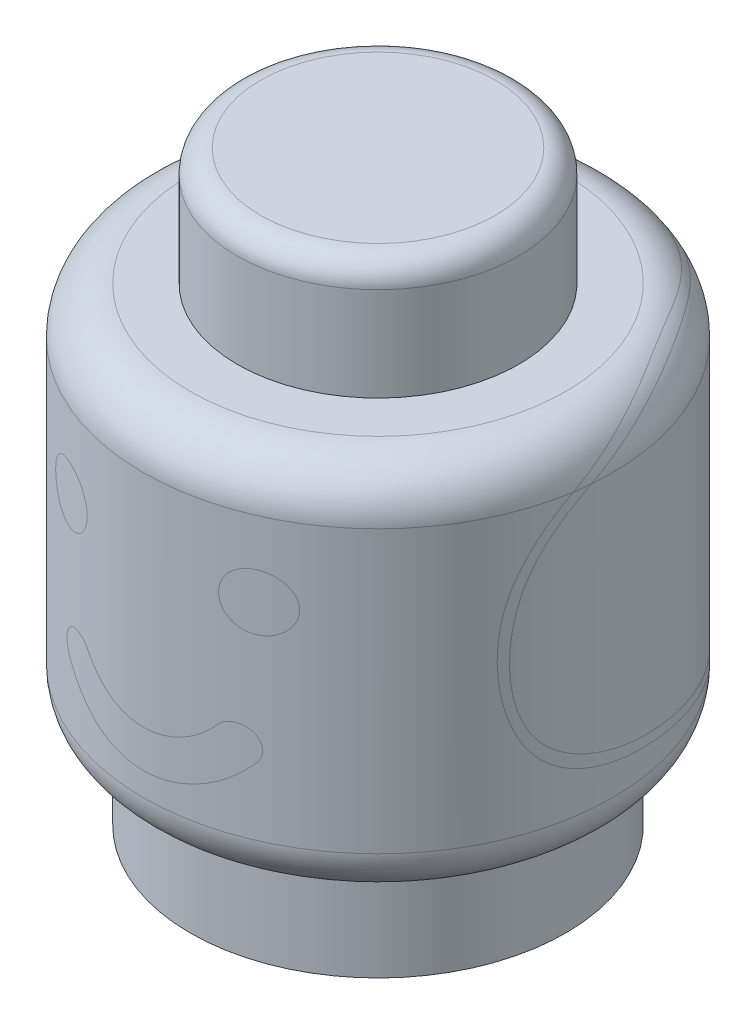
SolidWorks part; units mm, degrees
material "ABS"
ref_plane "Front" through (0, 0, 0) normal (0, 0, 1) x (1, 0, 0)
ref_plane "Top" through (0, 0, 0) normal (0, 1, 0) x (1, 0, 0)
ref_plane "Right" through (0, 0, 0) normal (1, 0, 0) x (0, 0, -1)
sketch "Sketch1" plane through (0, 0, 0) normal (0, 1, 0) x (1, 0, 0)
  circle A0 centre (0, 0) radius 5
  dimension "D1" = 10
sketch "Sketch3" plane through (0, 0, 0) normal (0, 1, 0) x (1, 0, 0)
  circle A0 centre (0, 0) radius 4
  dimension "D1" = 8
extrude "Head" add sketch "Sketch1" along normal blind 8
extrude "Neck" add sketch "Sketch3" against normal blind 2 contours A0
sketch "Sketch6" plane through (0, 8, 0) normal (0, 1, 0) x (1, 0, 0)
  circle A0 centre (0, 0) radius 3
  dimension "D1" = 6
extrude "Head knob" add sketch "Sketch6" along normal blind 2.5
hole_wizard "Head hole" positions "Sketch8" profile "Sketch7" hole size "Ø6.0" standard "ANSI Metric"
sketch "Sketch8" plane through (0, -2, 0) normal (0, -1, 0) x (-1, 0, 0)
  point P0 (0, 0)
sketch "Sketch7" plane through (0, -2, 0) normal (1, 0, 0) x (0, 0, -1)
  line L0 (0, 0) -> (0, 6.8026)
  line L1 (0, 6.8026) -> (3, 5)
  line L2 (3, 5) -> (3, 0)
  line L5 (3, 0) -> (0, 0)
  line L10 (0, 6.8026) -> (-3, 5) construction
  line L11 (0, -6.35) -> (0, 107.95) construction
  dimension "Hole Dia." = 6
  dimension "Hole Depth" = 5
  dimension "Drill Angle" = 118
fillet "Head roundness" radius 1 2 edges at (0, 0, 5) (0, 8, 5)
fillet "Smoothing edges" [suppressed] radius 0.1
fillet "Eady insert" radius 0.5 1 edges at (0, 10.5, 3)
sketch "Sketch9" plane through (0, 0, 0) normal (1, 0, 0) x (0, 0, -1)
  line L2 (-5, 7) -> (5, 7) construction
  line L3 (-0.4285, 7) -> (-0.5368, 7.1682) construction
  line L4 (-1.7145, 5.2338) -> (-1.9078, 5.2848) construction
  line L5 (-1.4811, 2.7691) -> (-1.6394, 2.6642) construction
  line L6 (4.9547, 7.2975) -> (5.0299, 7.4828) construction
  line L7 (8.9952, 4.1399) -> (9.1952, 4.1399) construction
  line L8 (4.9368, 0.6502) -> (4.8494, 0.416) construction
  arc A1 (4, 0) -> (5, 1) centre (4, 1) ccw construction
  arc A2 (5, 7) -> (4, 8) centre (4, 7) ccw construction
  spline S0 degree 3 poles (-0.3026, 7.6263) (-1.9595, 5.4032) (-1.8267, 1.2263) (2.4733, 2.0171) (6.7864, -0.4197) (10.8087, 5.0886) (6.7128, 6.5274) (3.1598, 8.0929) (-0.3026, 7.6263) (-1.9595, 5.4032) (-1.8267, 1.2263) knots -0.30846 -0.270009 -0.095471 0 0.100272 0.311612 0.353587 0.520022 0.69154 0.729991 0.904529 1 1.100272 1.311612 1.353587 only from (-1.7145, 5.2338) to (-1.7145, 5.2338)
  spline S1 degree 3 poles (-1.1206, 6.855) (-2.2574, 5.2283) (-1.6994, 0.8168) (1.903, 2.0367) (7.2209, -0.9272) (10.8858, 4.8178) (7.019, 6.935) (3.1436, 8.0116) (0.9956, 8.0417) (-1.1206, 6.855) (-2.2574, 5.2283) (-1.6994, 0.8168) knots -0.258073 -0.101406 -0.07364 0 0.09253 0.309613 0.353835 0.53475 0.703584 0.741927 0.898594 0.92636 1 1.09253 1.309613 1.353835 only from (-1.9078, 5.2848) to (-1.9078, 5.2848)
  dimension "D1" = 0.25
  dimension "D2" = 0.19
  dimension "D3" = 0.2
  dimension "D4" = 0.2
  dimension "D5" = 0.2
  dimension "D6" = 0.2
split line "Hairline"
sketch "Sketch10" plane through (0, 0, 0) normal (0, 0, 1) x (1, 0, 0)
  line L0 (0, 0) -> (0, 6.6973) construction
  line L1 (-1.6853, 2.6859) -> (0, 4.1) construction
  line L2 (0, 4.1) -> (1.6853, 2.6859) construction
  line L4 (4, 0) -> (-4, 0) construction
  circle A0 centre (-2, 5.4) radius 0.6
  circle A1 centre (2, 5.4) radius 0.6
  arc A2 (-1.6853, 2.6859) -> (1.6853, 2.6859) centre (0, 4.1) ccw construction
  arc A3 (-1.9917, 2.4288) -> (1.9917, 2.4288) centre (0, 4.1) ccw
  arc A4 (-1.3789, 2.943) -> (1.3789, 2.943) centre (0, 4.1) ccw
  arc A5 (-1.3789, 2.943) -> (-1.9917, 2.4288) centre (-1.6853, 2.6859) ccw
  arc A6 (1.9917, 2.4288) -> (1.3789, 2.943) centre (1.6853, 2.6859) ccw
  point P7 (0, 1.9)
  dimension "D1" = 1.2
  dimension "D2" = 1.2
  dimension "D3" = 0.4
  dimension "D4" = 50
  dimension "D5" = 4.1
  dimension "D6" = 2.2
  dimension "D7" = 5.4
  dimension "D8" = 5.4
  dimension "D9" = 2
  dimension "D10" = 2
split line "Facial features"
scale "Scale1" scale about centroid uniform scaling yes scale factor 2
